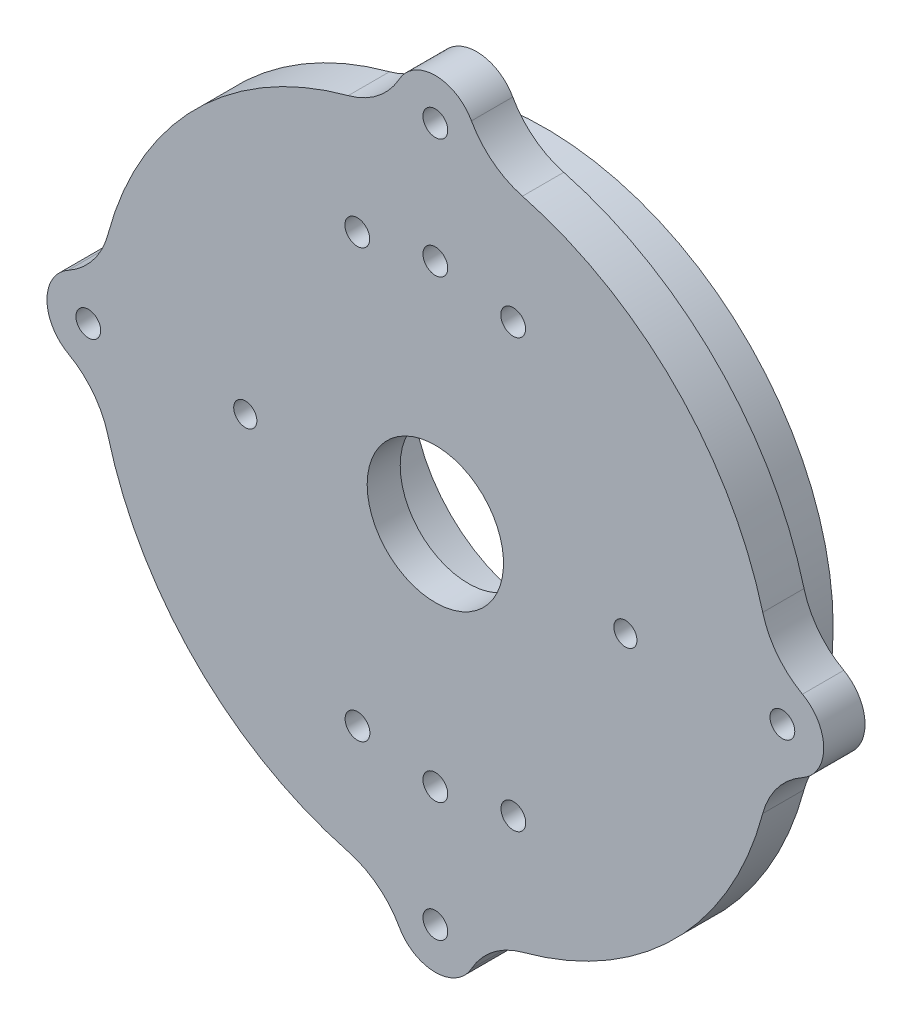
SolidWorks part; units mm, degrees
ref_plane "Ön Düzlem" through (0, 0, 0) normal (0, 0, 1) x (1, 0, 0)
ref_plane "Üst Düzlem" through (0, 0, 0) normal (0, 1, 0) x (1, 0, 0)
ref_plane "Sağ Düzlem" through (0, 0, 0) normal (1, 0, 0) x (0, 0, -1)
sketch "Çizim1" plane through (0, 0, 0) normal (0, 0, 1) x (1, 0, 0)
  circle A0 centre (0, 0) radius 16.1
  circle A1 centre (0, 0) radius 22.5
  circle A2 centre (0, 0) radius 34.9
  circle A3 centre (0, 0) radius 31
  dimension "D1" = 32.2
  dimension "D2" = 45
  dimension "D3" = 69.8
  dimension "D4" = 62
extrude "Yükseklik-Ekstrüzyon1" add sketch "Çizim1" along normal blind 8.25 contours A1 A0 | A2 A3 region at (-21.8636, 0, 0) region at (-33.9129, 0, 0)
sketch "Çizim2" plane through (0, 0, 8.25) normal (0, 0, 1) x (1, 0, 0)
  arc A6 (-10.5408, 39.6218) -> (-39.6218, 10.5408) centre (0, 0) ccw
  circle A7 centre (0, 42) radius 1.5
  arc A8 (4.3706, 44.4286) -> (-4.3706, 44.4286) centre (0, 42) ccw
  arc A9 (-4.3706, 44.4286) -> (-10.5408, 39.6218) centre (-13.1118, 49.2857) cw
  arc A10 (4.3706, 44.4286) -> (10.5408, 39.6218) centre (13.1118, 49.2857) ccw
  arc A11 (44.4286, 4.3706) -> (39.6218, 10.5408) centre (49.2857, 13.1118) cw
  arc A12 (44.4286, -4.3706) -> (44.4286, 4.3706) centre (42, 0) ccw
  circle A13 centre (42, 0) radius 1.5
  arc A14 (44.4286, -4.3706) -> (39.6218, -10.5408) centre (49.2857, -13.1118) ccw
  arc A15 (4.3706, -44.4286) -> (10.5408, -39.6218) centre (13.1118, -49.2857) cw
  arc A16 (-4.3706, -44.4286) -> (4.3706, -44.4286) centre (0, -42) ccw
  circle A17 centre (0, -42) radius 1.5
  arc A18 (-4.3706, -44.4286) -> (-10.5408, -39.6218) centre (-13.1118, -49.2857) ccw
  arc A19 (-44.4286, -4.3706) -> (-39.6218, -10.5408) centre (-49.2857, -13.1118) cw
  arc A20 (-44.4286, 4.3706) -> (-44.4286, -4.3706) centre (-42, 0) ccw
  circle A21 centre (-42, 0) radius 1.5
  arc A22 (-44.4286, 4.3706) -> (-39.6218, 10.5408) centre (-49.2857, 13.1118) ccw
  arc A23 (-39.6218, -10.5408) -> (-10.5408, -39.6218) centre (0, 0) ccw
  arc A24 (10.5408, -39.6218) -> (39.6218, -10.5408) centre (0, 0) ccw
  arc A25 (39.6218, 10.5408) -> (10.5408, 39.6218) centre (0, 0) ccw
  circle A26 centre (0, 0) radius 7.15
  point P0 (0, 0)
  point P17 (0, 0)
  point P48 (0, 0)
  dimension "D1" = 82
  dimension "D2" = 42
  dimension "D7" = 10
  dimension "D8" = 3
  dimension "D9" = 10
  dimension "D10" = 10
  dimension "D12" = 14.3
  dimension "D11" = 4
extrude "Yükseklik-Ekstrüzyon2" add sketch "Çizim2" along normal blind 5
sketch "Çizim7" plane through (0, 0, 8.25) normal (0, 0, -1) x (-1, 0, 0)
  circle A0 centre (0, 0) radius 16.1 construction
  circle A1 centre (0, 0) radius 16.1
extrude "Kes-Ekstrüzyon2" cut sketch "Çizim7" against normal blind 1
sketch "Çizim8" plane through (0, 0, 9.25) normal (0, 0, -1) x (-1, 0, 0)
  circle A0 centre (0, 0) radius 8.25
  dimension "D1" = 16.5
extrude "Kes-Ekstrüzyon3" cut sketch "Çizim8" against normal up to surface (4 mm away) up to face at (0, 0, 13.25)
sketch "Çizim9" plane through (0, 0, 13.25) normal (0, 0, 1) x (1, 0, 0)
  circle A0 centre (-23, 0) radius 1.4
  circle A1 centre (23, 0) radius 1.4
  dimension "D1" = 2.8
  dimension "D2" = 2.8
  dimension "D4" = 23
  dimension "D3" = 46
extrude "Kes-Ekstrüzyon4" cut sketch "Çizim9" against normal blind 25.4 contours A0 | A1
sketch "Çizim10" plane through (0, 0, 8.25) normal (0, 0, -1) x (-1, 0, 0)
  circle A0 centre (0, 27.5431) radius 1.5
  circle A1 centre (9.4433, 25.8737) radius 1.5
  circle A2 centre (-9.4203, 25.882) radius 1.5
  circle A3 centre (9.4203, -25.882) radius 1.5
  circle A4 centre (0, -27.5431) radius 1.5
  circle A5 centre (-9.4433, -25.8737) radius 1.5
  point P8 (0, 0)
  point P11 (0, 0)
  point P16 (0, 0)
  dimension "D1" = 3
  dimension "D2" = 2
  dimension "D3" = 2
  dimension "D4" = 9.4203
  dimension "D5" = 9.4433
  dimension "D6" = 27.5431
  dimension "D7" = 2
extrude "Kes-Ekstrüzyon5" cut sketch "Çizim10" against normal up to surface (5 mm away) up to face at (-21.6, 0, 13.25)
